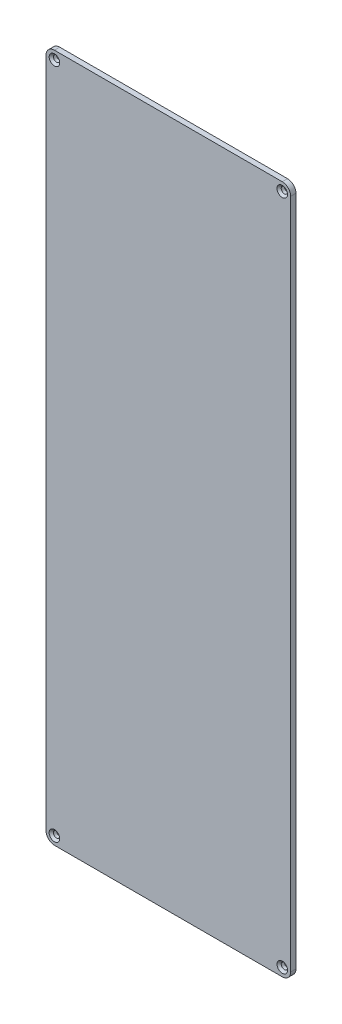
SolidWorks part; units mm, degrees
ref_plane "Front Plane" through (0, 0, 0) normal (0, 0, 1) x (1, 0, 0)
ref_plane "Top Plane" through (0, 0, 0) normal (0, 1, 0) x (1, 0, 0)
ref_plane "Right Plane" through (0, 0, 0) normal (1, 0, 0) x (0, 0, -1)
sketch "Sketch1" plane through (0, 0, 0) normal (0, 0, 1) x (1, 0, 0)
  line L0 (-1.5875, 127.142) -> (-1.5875, 0)
  line L1 (43.1165, 128.7295) -> (0, 128.7295)
  line L2 (44.704, 0) -> (44.704, 127.142)
  line L3 (0, -1.5875) -> (43.1165, -1.5875)
  line L4 (0, 0) -> (43.1165, 0) construction
  line L5 (43.1165, 0) -> (43.1165, 127.142) construction
  line L6 (43.1165, 127.142) -> (0, 127.142) construction
  line L7 (0, 127.142) -> (0, 0) construction
  arc A0 (0, 128.7295) -> (-1.5875, 127.142) centre (0, 127.142) ccw
  arc A1 (44.704, 127.142) -> (43.1165, 128.7295) centre (43.1165, 127.142) ccw
  arc A2 (43.1165, -1.5875) -> (44.704, 0) centre (43.1165, 0) ccw
  arc A3 (-1.5875, 0) -> (0, -1.5875) centre (0, 0) ccw
  circle A4 centre (43.1165, 0) radius 0.9 construction
  circle A5 centre (0, 0) radius 0.9 construction
  circle A6 centre (43.1165, 127.142) radius 0.9 construction
  circle A7 centre (0, 127.142) radius 0.9 construction
  point P2 (-1.5875, 127.1373)
  dimension "D5" = 1.8
  dimension "D1" = 46.2915
  dimension "D2" = 130.317
  dimension "D3" = 1.5875
extrude "Boss-Extrude1" add sketch "Sketch1" along normal blind 1
hole_wizard "CSK for M2 Flat Head Machine Screw1" positions "Sketch6" profile "Sketch4" countersink size "M2" standard "ANSI Metric" end condition up to next
sketch "Sketch6" plane through (0, 0, 1) normal (0, 0, 1) x (1, 0, 0)
  point P3 (43.1165, 127.142)
  point P6 (0, 0)
  point P9 (43.1165, 0)
  point P15 (0, 127.142)
  point P18 (0, 0)
  point P19 (-0.507, 127.649)
sketch "Sketch4" plane through (43.1165, 127.142, 1) normal (1, 0, 0) x (0, -1, 0)
  line L0 (0, 0) -> (0, 1)
  line L1 (0, 1) -> (0.6, 1)
  line L2 (0.6, 1) -> (0.6, 0.4)
  line L3 (0.6, 0.4) -> (1, 0)
  line L5 (1, 0) -> (0, 0)
  line L6 (-0.6, 0.4) -> (-1, 0) construction
  line L11 (0, -6.35) -> (0, 107.95) construction
  dimension "Thru Hole Dia." = 1.2
  dimension "Thru Hole Depth" = 1
  dimension "Near C'Sink Dia." = 2
  dimension "Near C'Sink Angle" = 90
